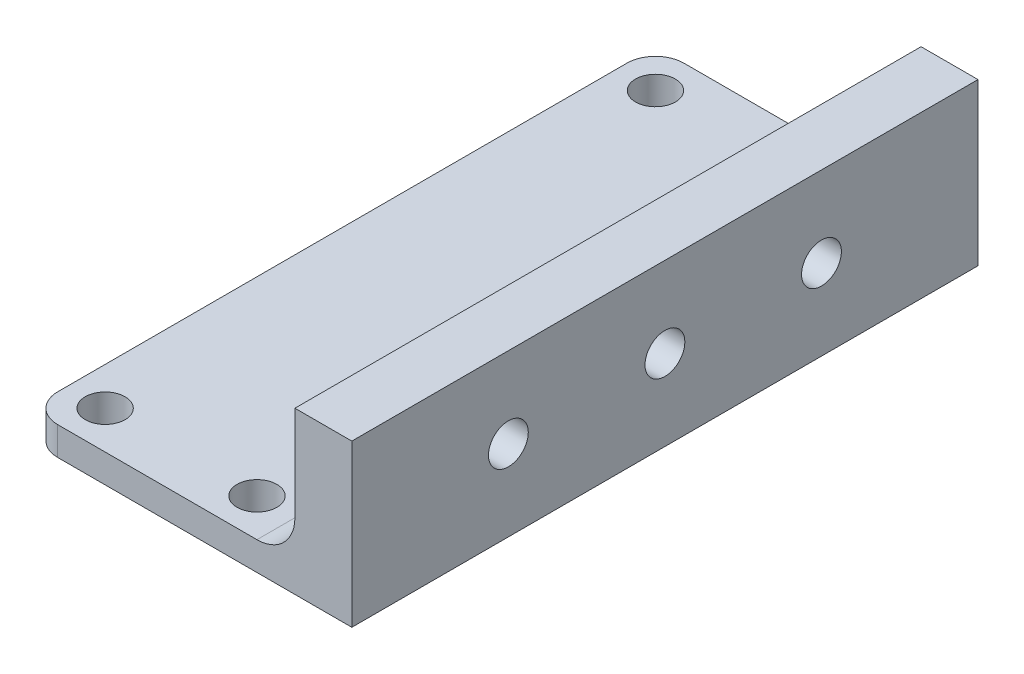
SolidWorks part; units mm, degrees
ref_plane "Front Plane" through (0, 0, 0) normal (0, 0, 1) x (1, 0, 0)
ref_plane "Top Plane" through (0, 0, 0) normal (0, 1, 0) x (1, 0, 0)
ref_plane "Right Plane" through (0, 0, 0) normal (1, 0, 0) x (0, 0, -1)
sketch "Sketch1" plane through (0, 0, 0) normal (0, 1, 0) x (1, 0, 0)
  line L0 (-14, 55.701) -> (-14, -10.299) construction
  line L1 (-26, 55.701) -> (8, 55.701)
  line L2 (-26, 55.701) -> (-26, -10.299)
  line L3 (-26, -10.299) -> (8, -10.299)
  line L4 (8, 55.701) -> (8, -10.299)
  circle A0 centre (-22, -6.299) radius 2.1
  circle A1 centre (-22, 51.701) radius 2.1
  circle A2 centre (-6, -6.299) radius 2.1
  circle A3 centre (-6, 51.701) radius 2.1
  dimension "D1" = 4.2
  dimension "D2" = 4.2
  dimension "D3" = 58
  dimension "D4" = 4
  dimension "D5" = 4
  dimension "D6" = 4
  dimension "D7" = 4
  dimension "D8" = 8
  dimension "D9" = 14
  dimension "D10" = 8
extrude "Boss-Extrude1" add sketch "Sketch1" along normal blind 3
sketch "Sketch2" plane through (0, 3, 0) normal (0, 1, 0) x (1, 0, 0)
  line L0 (-26, -10.299) -> (8, -10.299) construction
  line L1 (8, 55.701) -> (2, 55.701)
  line L2 (8, 55.701) -> (8, -10.299)
  line L3 (8, -10.299) -> (2, -10.299)
  line L4 (2, 55.701) -> (2, -10.299)
  dimension "D1" = 6
extrude "Boss-Extrude2" add sketch "Sketch2" along normal blind 14
sketch "Sketch3" plane through (8, 0, 0) normal (1, 0, 0) x (0, 0, -1)
  line L0 (22.701, 17) -> (22.701, 0) construction
  line L1 (-10.299, 17) -> (55.701, 17) construction
  line L2 (-10.299, 0) -> (55.701, 0) construction
  line L3 (-10.299, 8.5) -> (55.701, 8.5) construction
  line L4 (-10.299, 17) -> (-10.299, 0) construction
  line L5 (55.701, 17) -> (55.701, 0) construction
  circle A0 centre (22.701, 8.5) radius 2.1
  circle A1 centre (39.201, 8.5) radius 2.1
  circle A2 centre (6.201, 8.5) radius 2.1
  dimension "D1" = 4.2
  dimension "D2" = 4.2
  dimension "D3" = 16.5
extrude "Cut-Extrude1" cut sketch "Sketch3" against normal through all
chamfer "Chamfer1" distance 1 angle 45 3 edges at (2, 8.5, -8.301) (2, 8.5, -24.801) (2, 8.5, -41.301)
fillet "Fillet2" radius 4 1 edges at (2, 3, -22.701)
fillet "Fillet3" radius 3 2 edges at (-26, 1.5, 10.299) (-26, 1.5, -55.701)
